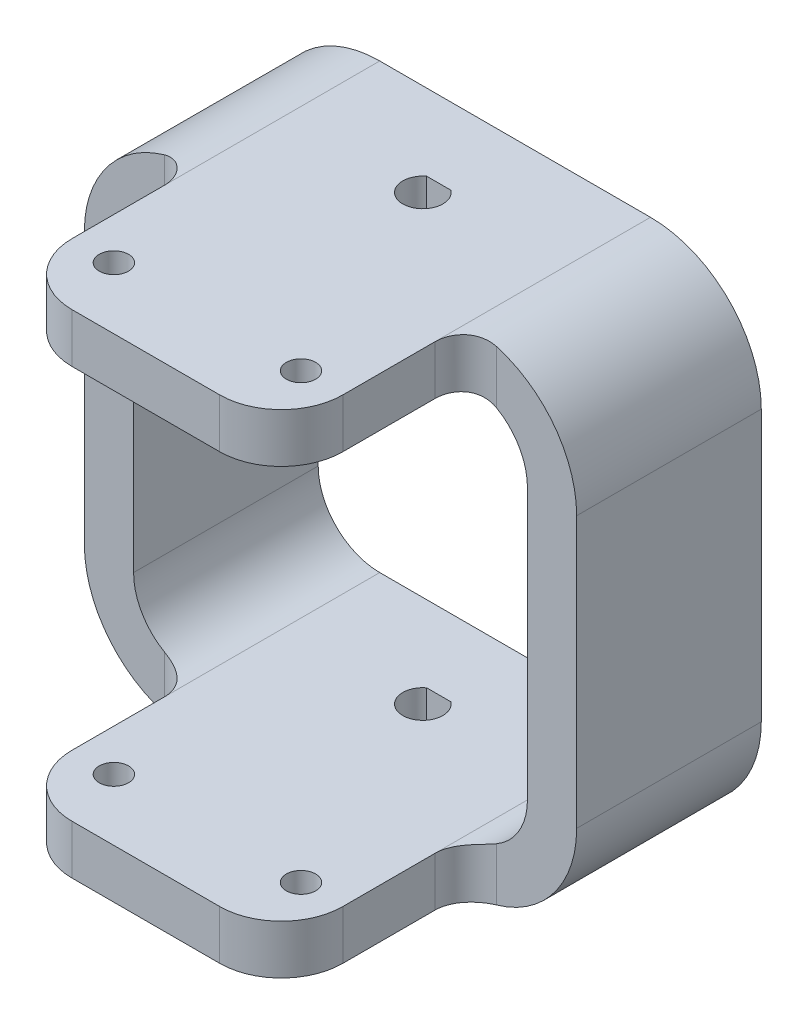
SolidWorks part; units mm, degrees
material "Plastique personnalisé"
ref_plane "Plan de face" through (0, 0, 0) normal (0, 0, 1) x (1, 0, 0)
ref_plane "Plan de dessus" through (0, 0, 0) normal (0, 1, 0) x (1, 0, 0)
ref_plane "Plan de droite" through (0, 0, 0) normal (1, 0, 0) x (0, 0, -1)
sketch "Esquisse1" plane through (0, 0, 0) normal (0, 0, 1) x (1, 0, 0)
  line L1 (40, -40) -> (-40, -40)
  line L2 (40, -40) -> (40, 40)
  line L3 (40, 40) -> (-40, 40)
  line L4 (-40, -40) -> (-40, 40)
  line L5 (40, -40) -> (-40, 40) construction
  line L6 (40, 40) -> (-40, -40) construction
  line L7 (-32, -32) -> (32, -32)
  line L8 (-32, -32) -> (-32, 32)
  line L9 (-32, 32) -> (32, 32)
  line L10 (32, -32) -> (32, 32)
  line L11 (-32, -32) -> (32, 32) construction
  line L12 (-32, 32) -> (32, -32) construction
  point P0 (0, 0)
  point P11 (0, 0)
  dimension "D1" = 8
  dimension "D3" = 80
extrude "Boss.-Extru.1" add sketch "Esquisse1" along normal mid plane 30
sketch "Esquisse2" plane through (0, 0, 0) normal (1, 0, 0) x (0, 0, -1)
  circle A0 centre (0, 0) radius 5
  dimension "D1" = 10
extrude "Enlèv. mat.-Extru.1" [suppressed] cut sketch "Esquisse2" against normal through all both and the other way through all
sketch "Esquisse3" plane through (0, -40, 0) normal (0, -1, 0) x (-1, 0, 0)
  circle A0 centre (0, 0) radius 5
  dimension "D1" = 10
extrude "Boss.-Extru.2" [suppressed] add sketch "Esquisse3" along normal blind 20
mirror "Symétrie1" [suppressed] about plane through (0, 0, 0) normal (0, 1, 0)
fillet "Congé2" radius 18 4 edges at (40, -40, 0) (-40, -40, 0) (-40, 40, 0) (40, 40, 0)
fillet "Congé3" radius 10 4 edges at (-32, 32, 0) (-32, -32, 0) (32, -32, 0) (32, 32, 0)
sketch "Esquisse5" [suppressed] plane through (0, -60, 0) normal (0, -1, 0) x (1, 0, 0)
  circle A0 centre (0, 0) radius 3
  circle A1 centre (0, 0) radius 5 construction
  dimension "D1" = 6
extrude "Boss.-Extru.3" [suppressed] add sketch "Esquisse5" along normal blind 15
sketch "Esquisse6" [suppressed] plane through (0, -75, 0) normal (0, -1, 0) x (1, 0, 0)
  line L1 (3, -3) -> (-3, -3)
  line L2 (3, -3) -> (3, -1.8)
  line L3 (3, -1.8) -> (-3, -1.8)
  line L4 (-3, -3) -> (-3, -1.8)
  circle A0 centre (0, 0) radius 3 construction
  dimension "D1" = 1.2
extrude "Enlèv. mat.-Extru.2" [suppressed] cut sketch "Esquisse6" against normal up to surface (15 mm away) contours L1 L4 L3 L2
sketch "Esquisse7" plane through (0, 0, 15) normal (0, 0, 1) x (1, 0, 0)
  line L0 (22, 40) -> (-22, 40) construction
  line L1 (22, 32) -> (-22, 32)
  line L2 (22, 32) -> (22, 40)
  line L3 (22, 40) -> (-22, 40)
  line L4 (-22, 32) -> (-22, 40)
  line L6 (22, 32) -> (-22, 32) construction
extrude "Boss.-Extru.4" add sketch "Esquisse7" along normal blind 30
hole_wizard "Perçage pour écrous auto-bloquants 300® #6 (SP)1" positions "Esquisse10" profile "Esquisse9" hole size "#6-32" standard "PEM® Inch" end condition through all
sketch "Esquisse10" plane through (0, 40, 0) normal (0, -1, 0) x (0, 0, -1)
  line L0 (-35, 15.205) -> (-35, -15.205) construction
  line L3 (-35, 0) -> (-45, 0) construction
  line L6 (-45, 22) -> (-45, -22) construction
  point P0 (-35, 15.205)
  point P2 (-35, -15.205)
  point P20 (-45, 0)
  dimension "D1" = 30.41
  dimension "D2" = 10
sketch "Esquisse9" plane through (15.205, 40, 35) normal (1, 0, 0) x (0, 0, 1)
  line L0 (0, 0) -> (0, 80)
  line L1 (0, 80) -> (2.3812, 80)
  line L2 (2.3812, 80) -> (2.3812, 0)
  line L5 (2.3812, 0) -> (0, 0)
  line L11 (0, -6.35) -> (0, 107.95) construction
  dimension "Diamètre du perçage jusqu'au prochain" = 4.7625
  dimension "Profondeur du perçage jusqu'au prochain" = 80
fillet "Congé1" radius 10 2 edges at (22, 36, 45) (-22, 36, 45)
mirror "Symétrie2" about plane through (0, 0, 0) normal (0, 1, 0) of "Boss.-Extru.4", "Perçage pour écrous auto-bloquants 300® #6 (SP)1", "Congé1"
fillet "Congé4" radius 5 4 edges at (-22, -36, 15) (-22, 36, 15) (22, -36, 15) (22, 36, 15)
sketch "Esquisse11" plane through (0, -40, -40) normal (0, 1, 0) x (1, 0, 0)
  line L0 (40, -40) -> (-40, -40) construction
  line L1 (40, -25) -> (40, -55) construction
  line L2 (-40, -55) -> (-40, -25) construction
  line L3 (1.9649, -37.405) -> (-1.9649, -37.405)
  arc A0 (-1.9649, -37.405) -> (1.9649, -37.405) centre (0, -40) ccw
  dimension "D1" = 6.51
  dimension "D2" = 5.85
extrude "Enlèv. mat.-Extru.3" cut sketch "Esquisse11" along normal through all
